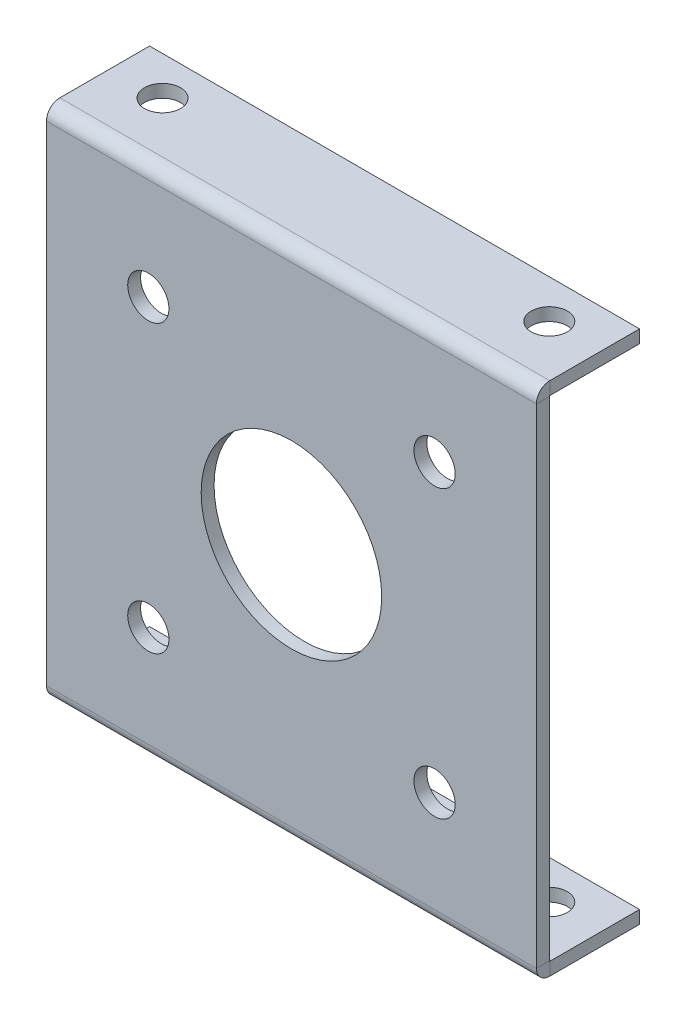
SolidWorks part; units mm, degrees
note: The reader was unsure of these and kept them because the rebuilt part matched: flange length of "Edge-Flange1", "Edge-Flange2".
material "ASTM A36 Steel"
ref_plane "Front Plane" through (0, 0, 0) normal (0, 0, 1) x (1, 0, 0)
ref_plane "Top Plane" through (0, 0, 0) normal (0, 1, 0) x (1, 0, 0)
ref_plane "Right Plane" through (0, 0, 0) normal (1, 0, 0) x (0, 0, -1)
sketch "Sketch1" plane through (0, 0, 0) normal (0, 0, 1) x (1, 0, 0)
  line L1 (-95, -100) -> (95, -100)
  line L2 (-95, -100) -> (-95, 100)
  line L3 (-95, 100) -> (95, 100)
  line L4 (95, -100) -> (95, 100)
  line L5 (-95, -100) -> (95, 100) construction
  line L6 (-95, 100) -> (95, -100) construction
  point P0 (0, 0)
  dimension "D1" = 190
  dimension "D2" = 200
base flange "Base-Flange1" sketch "Sketch1" thickness 5 reverse thickness direction no parameters "D1"=0.2
edge flange "Edge-Flange1" sketch "Sketch8" flange angle 90 flange length 40 flange position material inside bend radius 0.2 thickness 5 relief rectangular parameters "D6"=10
sketch "Sketch8" plane through (0, 100, -5) normal (0, -1, 0) x (-1, 0, 0)
  line L2 (-95, 0) -> (-95, 35)
  line L3 (-95, 35) -> (95, 35)
  line L4 (95, 35) -> (95, 0)
  line L9 (95, 0) -> (-95, 0) construction
  line L10 (95, 0) -> (-95, 0)
bend "EdgeBend1" bend radius 0.2 bend angle 90 parameters "D5"=1
edge flange "Edge-Flange2" sketch "Sketch11" flange angle 90 flange length 40 flange position material inside bend radius 0.2 thickness 5 relief rectangular parameters "D6"=10
sketch "Sketch11" plane through (0, -100, -5) normal (0, -1, 0) x (-1, 0, 0)
  line L2 (-95, 0) -> (-95, 35)
  line L3 (-95, 35) -> (95, 35)
  line L4 (95, 35) -> (95, 0)
  line L7 (95, 0) -> (-95, 0) construction
  line L8 (95, 0) -> (-95, 0)
bend "EdgeBend2" bend radius 0.2 bend angle 90 parameters "D5"=2
sketch "Sketch12" plane through (0, 0, 0) normal (0, 0, 1) x (1, 0, 0)
  circle A0 centre (0, 0) radius 35
  dimension "D1" = 70
extrude "Cut-Extrude1" cut sketch "Sketch12" against normal through all both and the other way through all normal cut yes
sketch "Sketch13" plane through (0, 0, 0) normal (0, 0, 1) x (1, 0, 0)
  circle A0 centre (55.5, 55.5) radius 8
  circle A1 centre (-55.5, 55.5) radius 8
  circle A2 centre (-55.5, -55.5) radius 8
  circle A3 centre (55.5, -55.5) radius 8
  point P0 (0, 0)
  dimension "D3" = 16
  dimension "D4" = 16
  dimension "D5" = 16
  dimension "D6" = 16
  dimension "D1" = 111
  dimension "D2" = 111
extrude "Cut-Extrude2" cut sketch "Sketch13" against normal through all both and the other way through all normal cut yes
sketch "Sketch14" plane through (0, -100, 0) normal (0, -1, 0) x (-1, 0, 0)
  line L0 (-95, 40) -> (-95, 5.2) construction
  line L1 (95, 5.2) -> (95, 40) construction
  line L2 (95, 40) -> (-95, 40) construction
  circle A0 centre (75, 25) radius 7
  circle A1 centre (-75, 25) radius 7
  dimension "D1" = 14
  dimension "D2" = 14
  dimension "D3" = 20
  dimension "D4" = 20
  dimension "D5" = 15
  dimension "D6" = 15
extrude "Cut-Extrude3" cut sketch "Sketch14" against normal through all both and the other way through all normal cut yes
sketch "Bend-Lines1" [suppressed] plane through (0, 0, 0) normal (0, 1, 0) x (1, 0, 0)
sketch "Bounding-Box1" [suppressed] plane through (0, 0, 0) normal (0, 1, 0) x (1, 0, 0)
sheet metal parameters "Sheet-Metal1" thickness 5 parameters "D1"=0.2
flat pattern "Flat-Pattern1" [suppressed]
sketch "Bend-Lines2" plane through (0, 0, 0) normal (0, 1, 0) x (1, 0, 0)
sketch3d "Bounding-Box2" [suppressed]
  line L0 (-85, 100, 0) -> (-85, -100, 0) construction
  line L1 (85, 100, 0) -> (85, -100, 0) construction
  line L2 (-85, 100, 0) -> (85, 100, 0) construction
  line L3 (-85, -100, 0) -> (85, -100, 0) construction
sheet metal parameters "Sheet-Metal2" thickness 5 parameters "D1"=0.2
flat pattern "Flat-Pattern1"
sketch "Bend-Lines2" plane through (0, 0, 0) normal (0, 0, 1) x (1, 0, 0)
  line L0 (85, 96.9206) -> (-85, 96.9206) construction
  line L1 (85, 96.9206) -> (-85, 96.9206) construction
sketch3d "Bounding-Box2" [suppressed]
  line L0 (85, 143.8412, 0) -> (85, -100, 0) construction
  line L1 (-85, 143.8412, 0) -> (-85, -100, 0) construction
  line L2 (85, 143.8412, 0) -> (-85, 143.8412, 0) construction
  line L3 (85, -100, 0) -> (-85, -100, 0) construction
bend of the flat pattern "Flatten-<EdgeBend1>1"
sheet metal parameters "Sheet-Metal3" thickness 5 parameters "D1"=0.2
flat pattern "Flat-Pattern1"
sketch "Bend-Lines2" plane through (0, 0, 0) normal (0, 0, 1) x (1, 0, 0)
  line L0 (85, 96.9206) -> (-85, 96.9206) construction
  line L1 (85, 96.9206) -> (-85, 96.9206) construction
  line L2 (-85, -96.9206) -> (85, -96.9206) construction
  line L3 (-85, -96.9206) -> (85, -96.9206) construction
sketch3d "Bounding-Box2" [suppressed]
  line L0 (85, 143.8412, 0) -> (85, -143.8412, 0) construction
  line L1 (-85, 143.8412, 0) -> (-85, -143.8412, 0) construction
  line L2 (85, 143.8412, 0) -> (-85, 143.8412, 0) construction
  line L3 (85, -143.8412, 0) -> (-85, -143.8412, 0) construction
bend of the flat pattern "Flatten-<EdgeBend1>1"
bend of the flat pattern "Flatten-<EdgeBend2>1"
sheet metal parameters "Sheet-Metal4" thickness 5 parameters "D1"=0.2
flat pattern "Flat-Pattern1"
sketch "Bend-Lines2" plane through (0, 0, 0) normal (0, 0, 1) x (1, 0, 0)
  line L0 (85, 96.9206) -> (-85, 96.9206) construction
  line L1 (85, 96.9206) -> (-85, 96.9206) construction
  line L2 (-85, -96.9206) -> (85, -96.9206) construction
  line L3 (-85, -96.9206) -> (85, -96.9206) construction
sketch3d "Bounding-Box2" [suppressed]
  line L0 (85, 143.8412, 0) -> (85, -143.8412, 0) construction
  line L1 (-85, 143.8412, 0) -> (-85, -143.8412, 0) construction
  line L2 (85, 143.8412, 0) -> (-85, 143.8412, 0) construction
  line L3 (85, -143.8412, 0) -> (-85, -143.8412, 0) construction
bend of the flat pattern "Flatten-<EdgeBend1>1"
bend of the flat pattern "Flatten-<EdgeBend2>1"
sheet metal parameters "Sheet-Metal5" thickness 5 parameters "D1"=0.2
flat pattern "Flat-Pattern1"
sketch "Bend-Lines2" plane through (0, 0, 0) normal (0, 0, 1) x (1, 0, 0)
  line L0 (85, 96.9206) -> (-85, 96.9206) construction
  line L1 (85, 96.9206) -> (-85, 96.9206) construction
  line L2 (-85, -96.9206) -> (85, -96.9206) construction
  line L3 (-85, -96.9206) -> (85, -96.9206) construction
sketch3d "Bounding-Box2" [suppressed]
  line L0 (85, 143.8412, 0) -> (85, -143.8412, 0) construction
  line L1 (-85, 143.8412, 0) -> (-85, -143.8412, 0) construction
  line L2 (85, 143.8412, 0) -> (-85, 143.8412, 0) construction
  line L3 (85, -143.8412, 0) -> (-85, -143.8412, 0) construction
bend of the flat pattern "Flatten-<EdgeBend1>1"
bend of the flat pattern "Flatten-<EdgeBend2>1"
sheet metal parameters "Sheet-Metal6" thickness 5 parameters "D1"=0.2
flat pattern "Flat-Pattern1"
sketch "Bend-Lines2" plane through (0, 0, 0) normal (0, 0, 1) x (1, 0, 0)
  line L0 (95, 96.9206) -> (-95, 96.9206) construction
  line L1 (95, 96.9206) -> (-95, 96.9206) construction
  line L2 (-95, -96.9206) -> (95, -96.9206) construction
  line L3 (-95, -96.9206) -> (95, -96.9206) construction
sketch3d "Bounding-Box2" [suppressed]
  line L0 (95, 133.8412, 0) -> (95, -133.8412, 0) construction
  line L1 (-95, 133.8412, 0) -> (-95, -133.8412, 0) construction
  line L2 (95, 133.8412, 0) -> (-95, 133.8412, 0) construction
  line L3 (95, -133.8412, 0) -> (-95, -133.8412, 0) construction
bend of the flat pattern "Flatten-<EdgeBend1>1"
bend of the flat pattern "Flatten-<EdgeBend2>1"
